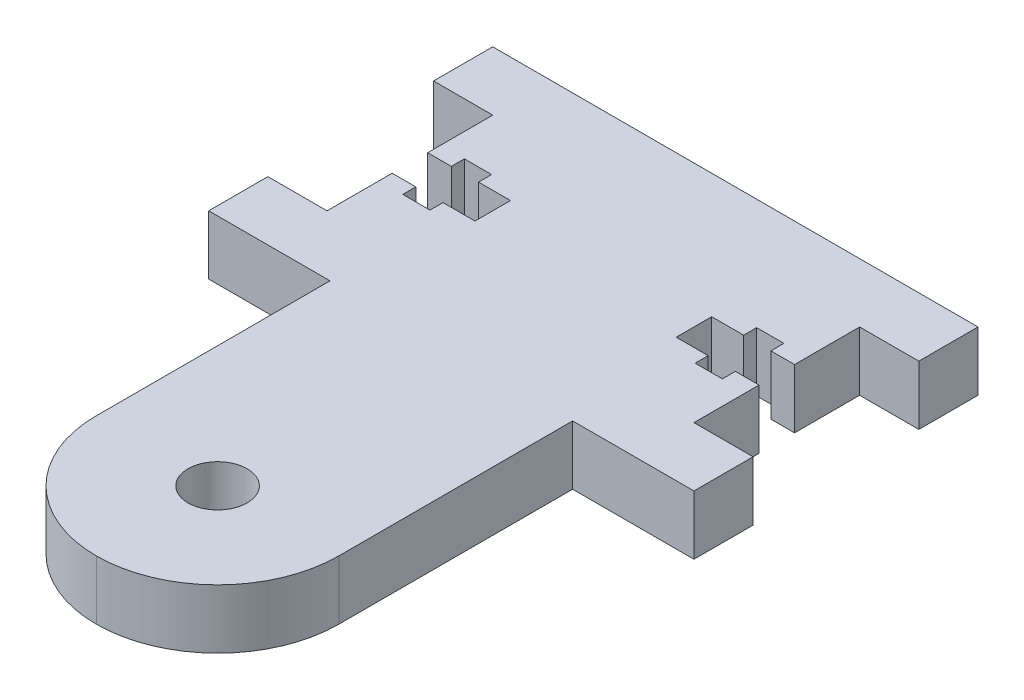
SolidWorks part; units mm, degrees
ref_plane "Front Plane" through (0, 0, 0) normal (0, 0, 1) x (1, 0, 0)
ref_plane "Top Plane" through (0, 0, 0) normal (0, 1, 0) x (1, 0, 0)
ref_plane "Right Plane" through (0, 0, 0) normal (1, 0, 0) x (0, 0, -1)
sketch "Sketch1" plane through (0, 0, 0) normal (0, 1, 0) x (1, 0, 0)
  line L0 (51.3755, 21.289) -> (44.3755, 18.289) construction
  line L1 (44.3755, 7.789) -> (75.3755, 7.789)
  line L2 (44.3755, 31.789) -> (75.3755, 31.789)
  line L3 (75.3755, 12.789) -> (75.3755, 18.289)
  line L4 (59.8755, 31.789) -> (59.8755, 7.789) construction
  line L5 (51.3755, 18.289) -> (44.3755, 21.289) construction
  line L6 (44.3755, 7.789) -> (39.3755, 7.789)
  line L7 (39.3755, 7.789) -> (39.3755, 12.789)
  line L8 (44.3755, 12.789) -> (44.3755, 18.289)
  line L9 (71.0755, 17.189) -> (73.3755, 17.189)
  line L10 (68.3755, 18.289) -> (71.0755, 18.289)
  line L11 (68.3755, 18.289) -> (68.3755, 21.289)
  line L12 (68.3755, 21.289) -> (71.0755, 21.289)
  line L13 (68.3755, 18.289) -> (75.3755, 21.289) construction
  line L14 (68.3755, 21.289) -> (75.3755, 18.289) construction
  line L15 (71.0755, 21.289) -> (71.0755, 22.389)
  line L16 (71.0755, 22.389) -> (73.3755, 22.389)
  line L17 (73.3755, 21.289) -> (73.3755, 22.389)
  line L18 (73.3755, 18.289) -> (73.3755, 17.189)
  line L19 (71.0755, 18.289) -> (71.0755, 17.189)
  line L20 (73.3755, 21.289) -> (75.3755, 21.289)
  line L21 (73.3755, 18.289) -> (75.3755, 18.289)
  line L22 (75.3755, 21.289) -> (75.3755, 26.789)
  line L23 (75.3755, 12.789) -> (80.3755, 12.789)
  line L24 (75.3755, 31.789) -> (80.3755, 31.789)
  line L25 (75.3755, 26.789) -> (80.3755, 26.789)
  line L26 (80.3755, 31.789) -> (80.3755, 26.789)
  line L27 (80.3755, 7.789) -> (80.3755, 12.789)
  line L28 (75.3755, 7.789) -> (80.3755, 7.789)
  line L29 (39.3755, 31.789) -> (39.3755, 26.789)
  line L30 (44.3755, 26.789) -> (39.3755, 26.789)
  line L31 (44.3755, 31.789) -> (39.3755, 31.789)
  line L32 (44.3755, 12.789) -> (39.3755, 12.789)
  line L33 (44.3755, 21.289) -> (44.3755, 26.789)
  line L34 (46.3755, 18.289) -> (44.3755, 18.289)
  line L35 (46.3755, 21.289) -> (44.3755, 21.289)
  line L36 (48.6755, 18.289) -> (48.6755, 17.189)
  line L37 (46.3755, 18.289) -> (46.3755, 17.189)
  line L38 (46.3755, 21.289) -> (46.3755, 22.389)
  line L39 (48.6755, 22.389) -> (46.3755, 22.389)
  line L40 (48.6755, 21.289) -> (48.6755, 22.389)
  line L41 (51.3755, 21.289) -> (48.6755, 21.289)
  line L42 (51.3755, 18.289) -> (51.3755, 21.289)
  line L43 (51.3755, 18.289) -> (48.6755, 18.289)
  line L44 (48.6755, 17.189) -> (46.3755, 17.189)
  line L45 (68.3755, 19.789) -> (59.8755, 19.789) construction
  point P23 (47.8755, 19.789)
  point P25 (71.8755, 19.789)
  point P44 (59.8755, 19.789)
  point P49 (0, 0)
  dimension "D2" = 31
  dimension "D3" = 3
  dimension "D4" = 5
  dimension "D5" = 5
  dimension "D6" = 2
  dimension "D7" = 2.3
  dimension "D8" = 2.7
  dimension "D9" = 1.1
  dimension "D10" = 5
  dimension "D11" = 24
extrude "Boss-Extrude1" add sketch "Sketch1" along normal blind 5
sketch "Sketch2" plane through (0, 5, 0) normal (0, 1, 0) x (1, 0, 0)
  line L0 (59.8755, 26.125) -> (59.8755, 6.125) construction
  line L1 (59.8755, 6.125) -> (59.8755, -7.211) construction
  line L2 (59.8755, -22.211) -> (59.8755, -11.961) construction
  line L3 (49.6255, -22.211) -> (70.1255, -22.211)
  line L4 (49.6255, -22.211) -> (49.6255, 7.789)
  line L5 (49.6255, 7.789) -> (70.1255, 7.789)
  line L6 (70.1255, -22.211) -> (70.1255, 7.789)
  line L7 (49.6255, -22.211) -> (70.1255, 7.789) construction
  line L8 (49.6255, 7.789) -> (70.1255, -22.211) construction
  line L9 (59.8755, -11.961) -> (58.7867, -13.0498) construction
  line L10 (59.8755, -11.961) -> (67.1337, -19.2192) construction
  line L11 (59.8755, 31.789) -> (59.8755, 7.789) construction
  line L12 (80.3755, 31.789) -> (39.3755, 31.789) construction
  line L13 (39.3755, 7.789) -> (80.3755, 7.789) construction
  circle A0 centre (59.8755, -11.961) radius 2.5
  dimension "D3" = 5
  dimension "D1" = 30
  dimension "D2" = 20.5
  dimension "D4" = 10.25
  dimension "D7" = 45
  dimension "D8" = 45
extrude "Boss-Extrude2" add sketch "Sketch2" against normal blind 5
fillet "Fillet1" radius 10.25 2 edges at (49.6255, 2.5, 22.211) (70.1255, 2.5, 22.211)
